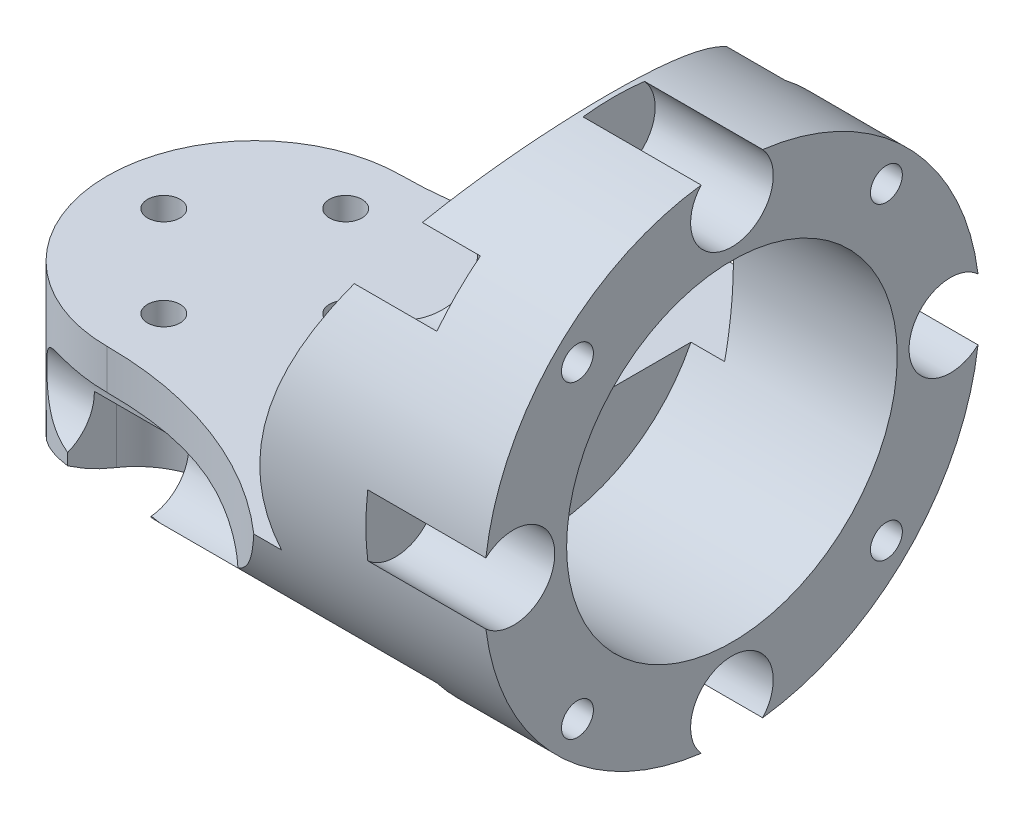
SolidWorks part; units mm, degrees
ref_plane "Front Plane" through (0, 0, 0) normal (0, 0, 1) x (1, 0, 0)
ref_plane "Top Plane" through (0, 0, 0) normal (0, 1, 0) x (1, 0, 0)
ref_plane "Right Plane" through (0, 0, 0) normal (1, 0, 0) x (0, 0, -1)
sketch "Sketch1" plane through (0, 0, 0) normal (0, 1, 0) x (1, 0, 0)
  line L0 (-7.7, 0) -> (0, 0) construction
  circle A0 centre (0, 0) radius 7.7 construction
  circle A1 centre (-7.7, 0) radius 1.375
  circle A3 centre (0, 7.7) radius 1.375
  circle A4 centre (7.7, 0) radius 1.375
  circle A5 centre (0, -7.7) radius 1.375
  circle A6 centre (0, 0) radius 12.5
  point P15 (0, 0)
  dimension "D1" = 15.4
  dimension "D2" = 2.75
  dimension "D4" = 25
  dimension "D3" = 4
extrude "Boss-Extrude1" add sketch "Sketch1" along normal blind 10
sketch "Sketch2" plane through (0, 10, 0) normal (0, 1, 0) x (1, 0, 0)
  line L0 (-34.4677, 0) -> (30.7737, 0) construction
  line L1 (23.1267, 23.2887) -> (40.4085, 23.2887)
  line L2 (0, 12.5) -> (0, 0) construction
  line L3 (23.1267, -23.2887) -> (40.4085, -23.2887)
  line L4 (40.4085, 23.2887) -> (40.4085, -23.2887)
  line L5 (40.4085, 20.9394) -> (40.4085, 1.5938) construction
  arc A0 (23.1267, 23.2887) -> (0, 12.5) centre (0, 42.6816) cw
  circle A1 centre (0, 0) radius 12.5 construction
  arc A2 (23.1267, -23.2887) -> (0, -12.5) centre (0, -42.6816) ccw
  arc A3 (0, 12.5) -> (0, -12.5) centre (0, 0) cw
extrude "Boss-Extrude2" add sketch "Sketch2" against normal blind 20
sketch "Sketch3" plane through (0, 0, 0) normal (0, -1, 0) x (1, 0, 0)
  line L0 (23.1267, -23.2887) -> (40.4085, -23.2887)
  line L1 (40.4085, -23.2887) -> (40.4085, 23.2887)
  line L2 (92.4683, 0) -> (42.5897, 0) construction
  line L3 (40.4085, 23.2887) -> (40.4085, -23.2887) construction
  line L4 (40.4085, 0) -> (30, 0) construction
  line L5 (23.1267, 23.2887) -> (40.4085, 23.2887)
  line L6 (40.4085, -23.2887) -> (23.1267, -23.2887) construction
  arc A0 (21.2136, 21.2128) -> (21.2136, -21.2128) centre (0, 0) cw
  arc A1 (-26.0234, -8.89) -> (-23.8162, 13.7492) centre (0, 0) ccw construction
  arc A2 (23.1267, -23.2887) -> (0, -12.5) centre (0, -42.6816) ccw construction
  arc A4 (21.2136, -21.2128) -> (23.1267, -23.2887) centre (0, -42.6816) cw
  arc A5 (23.1267, -23.2887) -> (0, -12.5) centre (0, -42.6816) ccw construction
  arc A6 (21.2136, 21.2128) -> (23.1267, 23.2887) centre (0, 42.6816) ccw
  dimension "D1" = 30
extrude "Boss-Extrude3" add sketch "Sketch3" along normal blind 21 and the other way blind 45
sketch "Sketch12" plane through (0, 0, 0) normal (0, -1, 0) x (1, 0, 0)
  circle A0 centre (0, 7.7) radius 1.375 construction
  circle A1 centre (7.7, 0) radius 1.375 construction
  arc A2 (0, -12.5) -> (0, 12.5) centre (0, 0) ccw
  arc A3 (0, 12.5) -> (0, -12.5) centre (0, 0) ccw
  arc A4 (0, -12.5) -> (0, 12.5) centre (0, 0) ccw
  arc A5 (0, 12.5) -> (0, -12.5) centre (0, 0) ccw
  circle A6 centre (0, -7.7) radius 1.375 construction
  circle A7 centre (-7.7, 0) radius 1.375 construction
  circle A8 centre (0, 7.7) radius 1.375
  circle A9 centre (7.7, 0) radius 1.375
  circle A10 centre (0, -7.7) radius 1.375
  circle A11 centre (-7.7, 0) radius 1.375
  dimension "D1" = 0
extrude "Boss-Extrude4" add sketch "Sketch12" along normal up to surface (10 mm away) up to face at (16.3583, -10, 0)
sketch "Sketch4" plane through (40.4085, 0, 0) normal (1, 0, 0) x (0, 0, -1)
  circle A0 centre (0, 16.25) radius 21
  circle A1 centre (0, 16.25) radius 21 construction
  circle A2 centre (0, 16.25) radius 128.8341
  dimension "D1" = 42
extrude "Cut-Extrude1" cut sketch "Sketch4" against normal blind 61
sketch "Sketch5" plane through (40.4085, 0, 0) normal (1, 0, 0) x (0, 0, -1)
  line L0 (-31.0802, 16.25) -> (31.1368, 16.25) construction
  line L1 (0, 16.25) -> (13.0815, 29.3315) construction
  circle A0 centre (0, 16.25) radius 14
  circle A1 centre (0, 16.25) radius 21 construction
  circle A2 centre (13.0815, 29.3315) radius 1.35 construction
  circle A3 centre (18.5, 16.25) radius 3.5 construction
  circle A4 centre (0, 16.25) radius 18.5 construction
  point P12 (0, 0)
  point P16 (0, 0)
  point P17 (0, 0)
  point P18 (0, 0)
  dimension "D1" = 28
  dimension "D3" = 37
  dimension "D4" = 2.7
  dimension "D5" = 7
  dimension "D2" = 45
extrude "Cut-Extrude2" cut sketch "Sketch5" against normal blind 16
sketch "Sketch6" plane through (40.4085, 0, 0) normal (1, 0, 0) x (0, 0, -1)
  circle A0 centre (18.5, 16.25) radius 3.5 construction
  circle A1 centre (13.0815, 29.3315) radius 1.35 construction
  circle A2 centre (18.5, 16.25) radius 3.5 construction
  circle A3 centre (13.0815, 29.3315) radius 1.35
  circle A4 centre (13.0815, 3.1685) radius 1.35
  circle A5 centre (-13.0815, 3.1685) radius 1.35
  circle A6 centre (-13.0815, 29.3315) radius 1.35
  circle A7 centre (0, 16.25) radius 14 construction
  circle A8 centre (0, -2.25) radius 3.5 construction
  circle A9 centre (-18.5, 16.25) radius 3.5 construction
  circle A10 centre (0, 34.75) radius 3.5 construction
  point P6 (-8.8309, 39.8849)
  point P15 (0, 16.25)
  point P16 (0, 0)
  point P24 (0, 16.25)
  dimension "D1" = 4
  dimension "D2" = 4
extrude "Cut-Extrude3" cut sketch "Sketch6" against normal through all
sketch "Sketch8" plane through (40.4085, 0, 0) normal (1, 0, 0) x (0, 0, -1)
  circle A0 centre (18.5, 16.25) radius 3.5
  circle A1 centre (18.5, 16.25) radius 3.5 construction
extrude "Cut-Extrude4" cut sketch "Sketch8" against normal blind 10
ref_axis "Axis1" through (24.4085, 16.25, 0) along (1, 0, 0)
pattern_circular "CirPattern1" count 4 over 360 about axis through (24.4085, 16.25, 0) along (1, 0, 0) of "Cut-Extrude4"
ref_plane "Plane1" through (-15, 0, 0) normal (1, 0, 0) x (0, 0, -1)
sketch "Sketch9" plane through (-15, 0, 0) normal (1, 0, 0) x (0, 0, -1)
  circle A0 centre (13.0815, 29.3315) radius 1.35 construction
  circle A1 centre (-13.0815, 29.3315) radius 1.35 construction
  circle A2 centre (-13.0815, 3.1685) radius 1.35 construction
  circle A3 centre (13.0815, 3.1685) radius 1.35 construction
  circle A4 centre (13.0815, 29.3315) radius 1.35 construction
  circle A5 centre (-13.0815, 29.3315) radius 1.35 construction
  circle A6 centre (-13.0815, 3.1685) radius 1.35 construction
  circle A7 centre (13.0815, 3.1685) radius 1.35 construction
  circle A8 centre (13.0815, 29.3315) radius 3.5
  circle A9 centre (-13.0815, 3.1685) radius 3.5
  circle A10 centre (-13.0815, 29.3315) radius 3.5
  circle A11 centre (13.0815, 3.1685) radius 3.5
  point P19 (0, 0)
  point P20 (0, 0)
  point P21 (0, 0)
  dimension "D1" = 7
extrude "Cut-Extrude5" cut sketch "Sketch9" along normal blind 47
ref_plane "Plane2" through (0, -4.75, 0) normal (0, -1, 0) x (-1, 0, 0)
sketch "Sketch13" plane through (0, -4.75, 0) normal (0, -1, 0) x (-1, 0, 0)
  line L0 (-4, 7.7) -> (-4, 15.3399)
  line L1 (-4, 15.3399) -> (4, 15.3399)
  line L2 (4, 15.3399) -> (4, 7.7)
  circle A0 centre (0, 7.7) radius 1.375 construction
  arc A1 (4, 7.7) -> (-4, 7.7) centre (0, 7.7) ccw construction
  circle A4 centre (0, 7.7) radius 1.375 construction
  arc A8 (-4, 7.7) -> (4, 7.7) centre (0, 7.7) ccw
  dimension "D1" = 8
extrude "Cut-Extrude8" cut sketch "Sketch13" against normal blind 8
ref_axis "Axis2" through (0, -7.95, 0) along (0, 1, 0)
pattern_circular "CirPattern3" count 3 every 90 about axis through (0, -7.95, 0) along (0, 1, 0) of "Cut-Extrude8"
sketch "Sketch14" plane through (0, -4.75, 0) normal (0, -1, 0) x (-1, 0, 0)
  circle A0 centre (-7.7, 0) radius 1.375 construction
  circle A1 centre (-7.7, 0) radius 1.375 construction
  circle A2 centre (-7.7, 0) radius 4
  arc A3 (-4, 7.7) -> (4, 7.7) centre (0, 7.7) ccw construction
extrude "Cut-Extrude9" cut sketch "Sketch14" against normal blind 8
